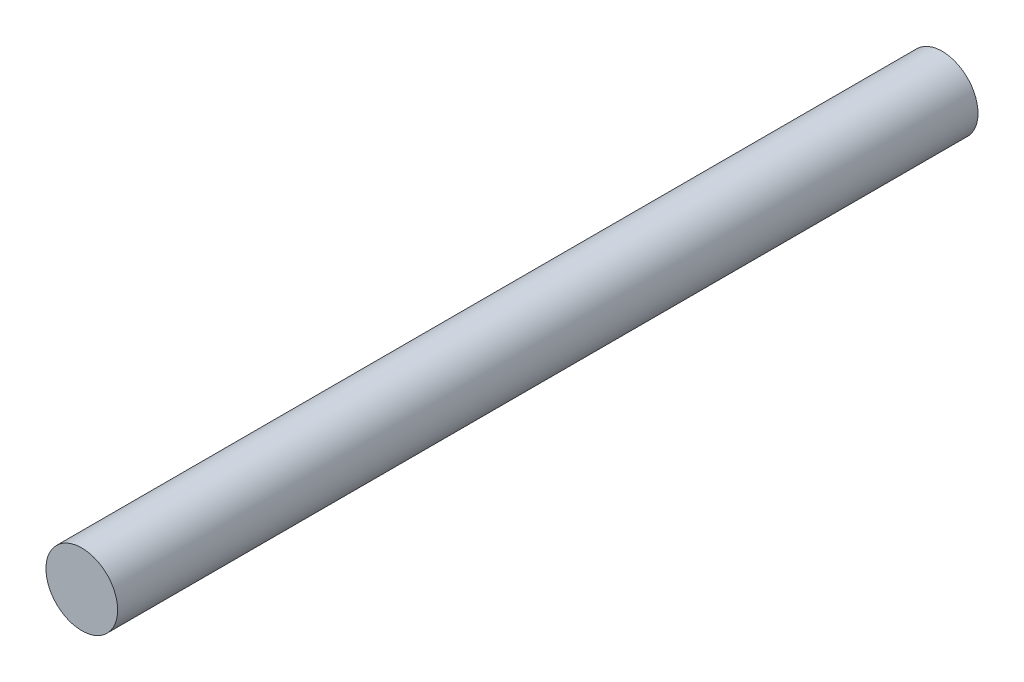
SolidWorks part; units mm, degrees
ref_plane "Front Plane" through (0, 0, 0) normal (0, 0, 1) x (1, 0, 0)
ref_plane "Top Plane" through (0, 0, 0) normal (0, 1, 0) x (1, 0, 0)
ref_plane "Right Plane" through (0, 0, 0) normal (1, 0, 0) x (0, 0, -1)
sketch "Sketch1" plane through (0, 0, 0) normal (0, 0, 1) x (1, 0, 0)
  circle A0 centre (0, 0) radius 4.7625
  dimension "D1" = 9.525
extrude "Boss-Extrude1" add sketch "Sketch1" along normal blind 114.3
